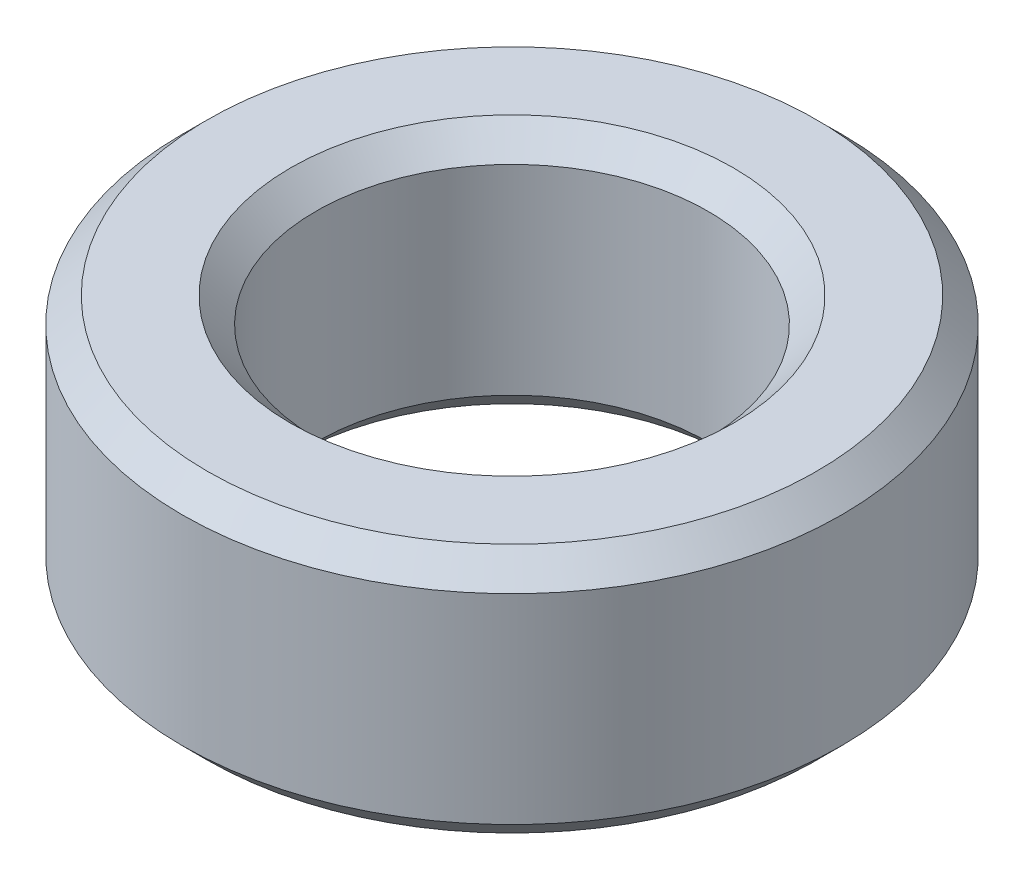
SolidWorks part; units mm, degrees
ref_plane "Front Plane" through (0, 0, 0) normal (0, 0, 1) x (1, 0, 0)
ref_plane "Top Plane" through (0, 0, 0) normal (0, 1, 0) x (1, 0, 0)
ref_plane "Right Plane" through (0, 0, 0) normal (1, 0, 0) x (0, 0, -1)
sketch "Sketch1" plane through (0, 0, 0) normal (0, 1, 0) x (1, 0, 0)
  circle A0 centre (0, 0) radius 27.5
  dimension "SLEEVE_OD" = 55
extrude "Boss-Extrude1" add sketch "Sketch1" along normal blind 20.8658
sketch "Sketch2" plane through (0, 0, 0) normal (0, 1, 0) x (1, 0, 0)
  circle A0 centre (0, 0) radius 16.3651
  dimension "BORE_D" = 32.7301
extrude "Cut-Extrude1" cut sketch "Sketch2" along normal through all
chamfer "Chamfer1" distance 2.0958 angle 45 4 edges at (0, 20.8658, 16.3651) (0, 0, 16.3651) (0, 0, 27.5) (0, 20.8658, 27.5)
